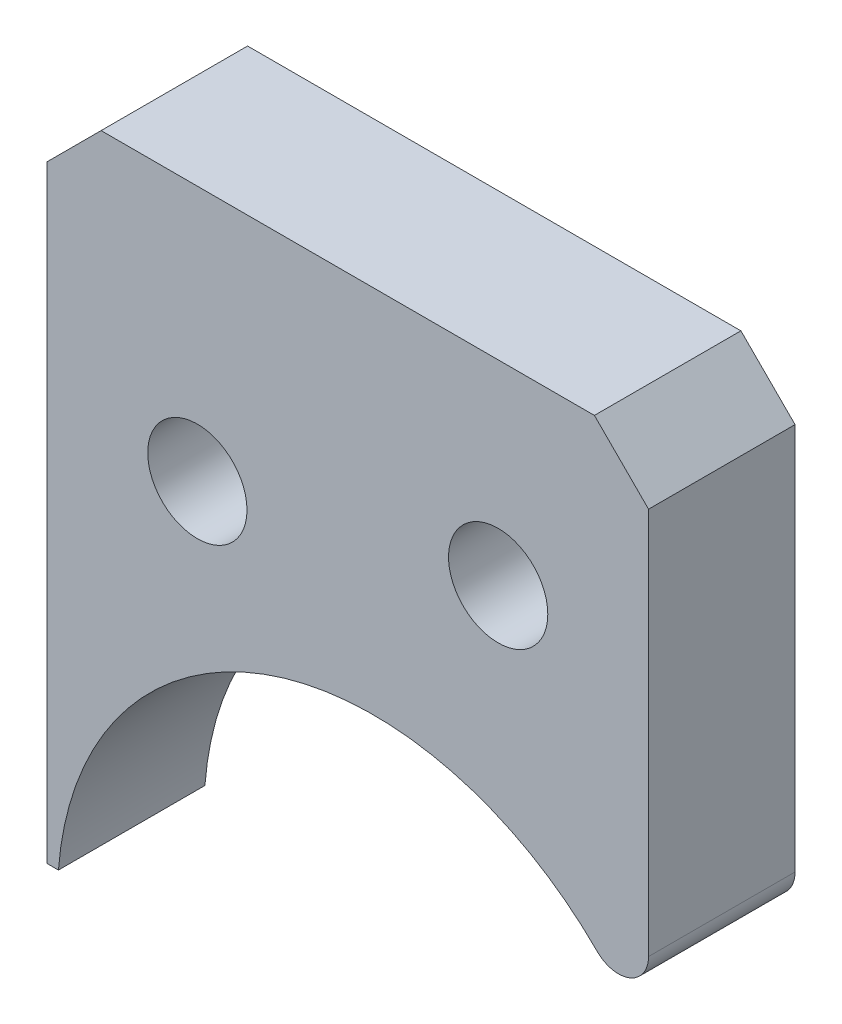
SolidWorks part; units mm, degrees
ref_plane "Front Plane" through (0, 0, 0) normal (0, 0, 1) x (1, 0, 0)
ref_plane "Top Plane" through (0, 0, 0) normal (0, 1, 0) x (1, 0, 0)
ref_plane "Right Plane" through (0, 0, 0) normal (1, 0, 0) x (0, 0, -1)
sketch "Sketch1" plane through (0, 0, 0) normal (0, 0, 1) x (1, 0, 0)
  line L0 (0, 22) -> (20, 22)
  line L1 (0, 0) -> (0.3816, 0)
  line L2 (0, 0) -> (0, 22)
  line L4 (20, 4.3589) -> (20, 22)
  arc A0 (20, 4.3589) -> (0.3816, 0) centre (10.8515, -0.7943) ccw
  point P3 (11.2872, -0.5489)
  dimension "10.5" = 10.5
  dimension "D1" = 17.6411
  dimension "D2" = 22
  dimension "D3" = 20
extrude "Boss-Extrude1" add sketch "Sketch1" along normal blind 4.87
sketch "Sketch2" plane through (0, 0, 4.87) normal (0, 0, 1) x (1, 0, 0)
  line L0 (5, 15.5) -> (11, 15.5) construction
  line L1 (11, 15.5) -> (15, 15.5) construction
  line L2 (11, 15.5) -> (11, 0) construction
  line L3 (5, 15.5) -> (5, 13.5) construction
  circle A0 centre (5, 13.5) radius 1.65
  circle A1 centre (15, 15.5) radius 1.65
  dimension "D5" = 15.5
  dimension "D4" = 3.3
  dimension "D1" = 11
  dimension "D2" = 6
  dimension "D3" = 2
  dimension "D6" = 4
extrude "Cut-Extrude1" cut sketch "Sketch2" against normal blind 4.87
chamfer "Chamfer1" distance 1.8 angle 45 2 edges at (20, 22, 2.435) (0, 22, 2.435)
fillet "Fillet1" radius 0.5 rebuild error yes
fillet "Fillet2" radius 1 1 edges at (20, 4.3589, 2.435)
